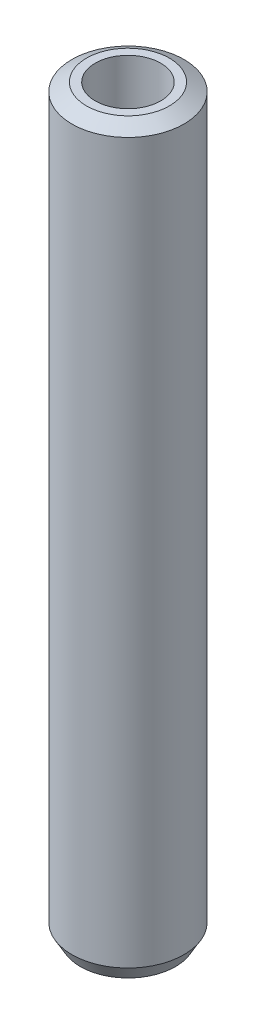
SolidWorks part; units mm, degrees
ref_plane "Front Plane" through (0, 0, 0) normal (0, 0, 1) x (1, 0, 0)
ref_plane "Top Plane" through (0, 0, 0) normal (0, 1, 0) x (1, 0, 0)
ref_plane "Right Plane" through (0, 0, 0) normal (1, 0, 0) x (0, 0, -1)
sketch "Sketch1" plane through (0, 0, 0) normal (0, 1, 0) x (1, 0, 0)
  circle A0 centre (0, 0) radius 10
  dimension "SHAFT_OD" = 20
extrude "Boss-Extrude1" add sketch "Sketch1" along normal blind 132.5109
sketch "Sketch2" plane through (0, 0, 0) normal (0, 1, 0) x (1, 0, 0)
  circle A0 centre (0, 0) radius 5.845
  dimension "BORE_D" = 11.69
extrude "Cut-Extrude1" cut sketch "Sketch2" along normal through all
chamfer "Chamfer1" distance 1.5021 angle 60 2 edges at (0, 132.5109, 10) (0, 0, 10) first distance on face at (0, 132.5109, 10) first distance on face at (0, 0, 5.845)
